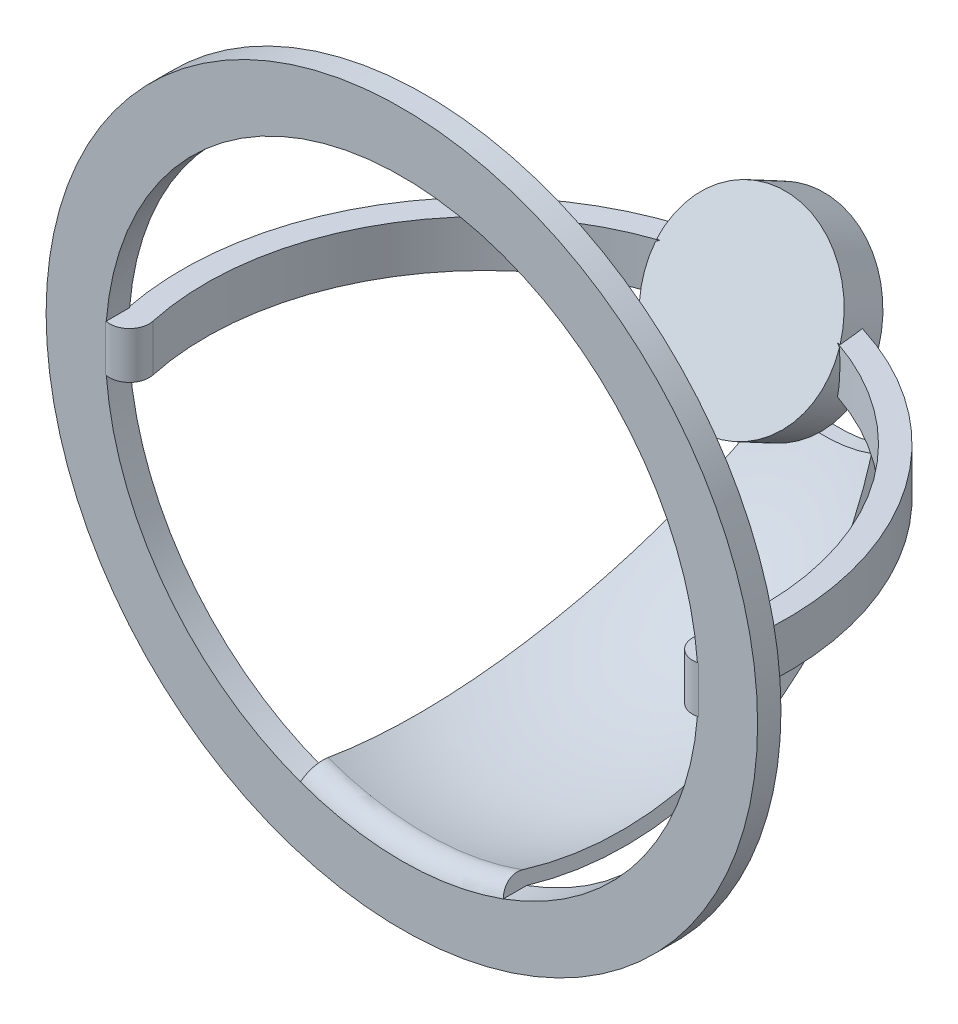
SolidWorks part; units mm, degrees
ref_plane "Front Plane" through (0, 0, 0) normal (0, 0, 1) x (1, 0, 0)
ref_plane "Top Plane" through (0, 0, 0) normal (0, 1, 0) x (1, 0, 0)
ref_plane "Right Plane" through (0, 0, 0) normal (1, 0, 0) x (0, 0, -1)
sketch "Sketch1" plane through (0, 0, 0) normal (0, 0, 1) x (1, 0, 0)
  circle A0 centre (0, 0) radius 15.24
  circle A1 centre (0, 0) radius 12.7
  dimension "D1" = 2.54
  dimension "D2" = 25.4
extrude "Boss-Extrude1" add sketch "Sketch1" along normal blind 1
sketch "Sketch2" plane through (0, 0, 0) normal (0, 1, 0) x (1, 0, 0)
  line L0 (12.7, 0) -> (12.7, 2.54) construction
  line L1 (12.7, -1) -> (12.7, 0) construction
  line L2 (12.7, 2.54) -> (0, 2.54) construction
  line L3 (-3.81, 13.8511) -> (3.81, 13.8511) construction
  line L7 (-12.7, 0) -> (-12.7, -1) construction
  line L8 (-15.24, -1) -> (15.24, -1) construction
  line L12 (15.24, 0) -> (-15.24, 0) construction
  line L13 (0, -1) -> (0, 19.32) construction
  line L15 (-12.7, -1) -> (-12.7, 0)
  line L16 (12.7, 0) -> (12.7, -1)
  line L18 (12.7, 0) -> (-12.7, 0) construction
  line L19 (-3.81, 13.8511) -> (-3.81, 14.9184)
  line L20 (3.81, 13.8511) -> (3.81, 14.9184)
  arc A4 (12.7, 0) -> (3.81, 14.9184) centre (0, 2.54) ccw
  arc A5 (-11.6621, 0) -> (-3.81, 13.8511) centre (0, 2.54) cw
  arc A6 (-3.81, 14.9184) -> (-12.7, 0) centre (0, 2.54) ccw
  arc A7 (3.81, 13.8511) -> (11.6621, 0) centre (0, 2.54) cw
  arc A8 (-11.6621, 0) -> (-12.7, -1) centre (-12.4892, -0.1801) cw
  arc A9 (11.6621, 0) -> (12.7, -1) centre (12.4892, -0.1801) ccw
  dimension "D1" = 1.016
  dimension "D2" = 7.62
  dimension "D3" = 20.32
  dimension "D4" = 2.54
extrude "Boss-Extrude2" add sketch "Sketch2" along normal blind 1 and the other way blind 1
ref_plane "Plane1" through (0, -5.9751, -11.196) normal (0, 0.4708, 0.8822) x (1, 0, 0)
sketch "Sketch3" plane through (0, -5.9751, -11.196) normal (0, 0.4708, 0.8822) x (1, 0, 0)
  circle A0 centre (0, 6.7727) radius 3.975
extrude "Boss-Extrude3" add sketch "Sketch3" along normal up to vertex (0.9417 mm away) and the other way up to vertex (0.9417 mm away) up to point (3.81, 1, -13.8511) other way up to point (3.81, -1, -14.9184)
sketch "Sketch6" plane through (0, 0, 0) normal (1, 0, 0) x (0, 0, -1)
  line L0 (0, 0) -> (21.8954, 0) construction
  line L1 (0, -15.24) -> (0, 15.24) construction
  point P4 (0, 0)
sketch "Sketch4" plane through (0, 0, 0) normal (1, 0, 0) x (0, 0, -1)
  line L0 (0, -15.24) -> (0, 15.24) construction
  line L1 (17.0871, -5.9669) -> (17.705, -5.9669)
  line L2 (17.0871, -5.9669) -> (17.0871, 3.0635) construction
  line L4 (0, -12.7) -> (-1, -12.7)
  line L6 (0, -12.7) -> (0, -1) construction
  arc A0 (0, -12.7) -> (17.705, -5.9669) centre (4.0599, 3.269) ccw
  arc A1 (0, -12.1753) -> (17.0871, -5.9669) centre (4.0599, 3.269) ccw
  arc A2 (0, -12.1753) -> (-1, -12.7) centre (-0.2128, -12.9849) ccw
  dimension "D1" = 0.508
revolve "Revolve1" add sketch "Sketch4" angle 20 about L0 other way angle 20
